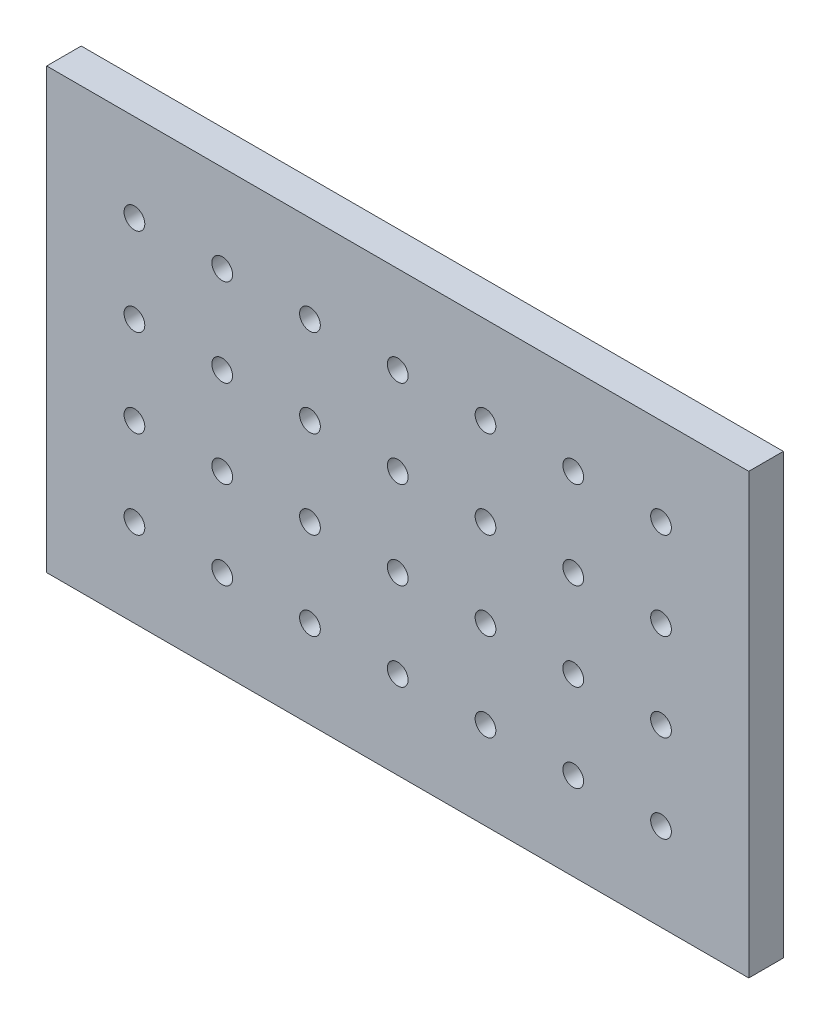
SolidWorks part; units mm, degrees
ref_plane "Front Plane" through (0, 0, 0) normal (0, 0, 1) x (1, 0, 0)
ref_plane "Top Plane" through (0, 0, 0) normal (0, 1, 0) x (1, 0, 0)
ref_plane "Right Plane" through (0, 0, 0) normal (1, 0, 0) x (0, 0, -1)
sketch "Sketch1" plane through (0, 0, 0) normal (0, 0, 1) x (1, 0, 0)
  line L1 (0, 0) -> (-203.2, 0)
  line L2 (0, 0) -> (0, -127)
  line L3 (0, -127) -> (-203.2, -127)
  line L4 (-203.2, 0) -> (-203.2, -127)
  dimension "D1" = 203.2
  dimension "D2" = 127
extrude "Boss-Extrude1" add sketch "Sketch1" along normal blind 10
sketch "Sketch2" plane through (0, 0, 10) normal (0, 0, 1) x (1, 0, 0)
  line L0 (0, 0) -> (-203.2, 0) construction
  line L1 (-203.2, 0) -> (-203.2, -127) construction
  circle A0 centre (-177.8, -25.4) radius 3
  circle A1 centre (-152.4, -25.4) radius 3
  circle A2 centre (-127, -25.4) radius 3
  circle A3 centre (-101.6, -25.4) radius 3
  circle A4 centre (-76.2, -25.4) radius 3
  circle A5 centre (-50.8, -25.4) radius 3
  circle A6 centre (-25.4, -25.4) radius 3
  circle A7 centre (-152.4, -50.8) radius 3
  circle A8 centre (-127, -50.8) radius 3
  circle A9 centre (-101.6, -50.8) radius 3
  circle A10 centre (-76.2, -50.8) radius 3
  circle A11 centre (-50.8, -50.8) radius 3
  circle A12 centre (-25.4, -50.8) radius 3
  circle A13 centre (-152.4, -76.2) radius 3
  circle A14 centre (-127, -76.2) radius 3
  circle A15 centre (-101.6, -76.2) radius 3
  circle A16 centre (-76.2, -76.2) radius 3
  circle A17 centre (-50.8, -76.2) radius 3
  circle A18 centre (-25.4, -76.2) radius 3
  circle A19 centre (-152.4, -101.6) radius 3
  circle A20 centre (-127, -101.6) radius 3
  circle A21 centre (-101.6, -101.6) radius 3
  circle A22 centre (-76.2, -101.6) radius 3
  circle A23 centre (-50.8, -101.6) radius 3
  circle A24 centre (-25.4, -101.6) radius 3
  circle A25 centre (-177.8, -50.8) radius 3
  circle A26 centre (-177.8, -76.2) radius 3
  circle A27 centre (-177.8, -101.6) radius 3
  dimension "D1" = 25.4
  dimension "D2" = 25.4
  dimension "D3" = 6
  dimension "D4" = 7
  dimension "D5" = 4
extrude "Cut-Extrude1" cut sketch "Sketch2" against normal up to next (10 mm away)
equation "\"inch\"=25.4"
equation "\"D2@Sketch2\"=\"inch\""
equation "\"D1@Sketch2\"=\"inch\""
equation "\"D2@Sketch1\"=\"inch\"*5"
equation "\"D1@Sketch1\"=\"inch\"*8"
